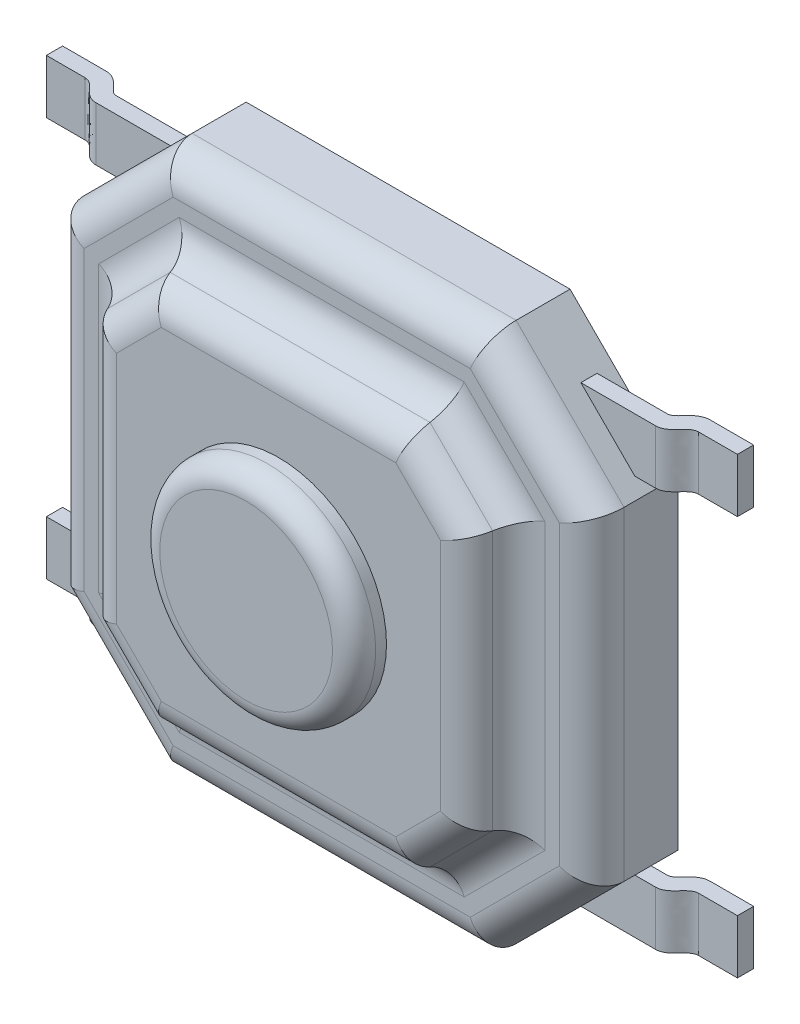
SolidWorks part; units mm, degrees
ref_plane "Front Plane" through (0, 0, 0) normal (0, 0, 1) x (1, 0, 0)
ref_plane "Top Plane" through (0, 0, 0) normal (0, 1, 0) x (1, 0, 0)
ref_plane "Right Plane" through (0, 0, 0) normal (1, 0, 0) x (0, 0, -1)
sketch "Sketch1" plane through (0, 0, 0) normal (0, 0, 1) x (1, 0, 0)
  line L0 (0, 0) -> (0, 2.5) construction
  line L1 (0, 0) -> (2.5, 0) construction
  line L2 (-1.5, 2.5) -> (1.5, 2.5)
  line L3 (1.5, 2.5) -> (2.5, 1.5)
  line L4 (2.5, 1.5) -> (2.5, -1.5)
  line L5 (1.5, -2.5) -> (2.5, -1.5)
  line L6 (-1.5, -2.5) -> (1.5, -2.5)
  line L7 (-1.5, -2.5) -> (-2.5, -1.5)
  line L8 (-2.5, 1.5) -> (-2.5, -1.5)
  line L9 (-1.5, 2.5) -> (-2.5, 1.5)
  point P13 (0, -2.5)
  dimension "D1" = 45
  dimension "D2" = 2.5
  dimension "D3" = 1.5
extrude "Boss-Extrude1" add sketch "Sketch1" along normal blind 0.8
sketch "Sketch2" plane through (0, 0, 0.8) normal (0, 0, 1) x (1, 0, 0)
  line L46 (-1.2101, 1.8) -> (-1.8, 1.2101)
  line L47 (-1.8, 1.2101) -> (-1.8, -1.2101)
  line L48 (-1.8, -1.2101) -> (-1.2101, -1.8)
  line L49 (-1.2101, -1.8) -> (1.2101, -1.8)
  line L50 (1.2101, -1.8) -> (1.8, -1.2101)
  line L51 (1.8, -1.2101) -> (1.8, 1.2101)
  line L52 (1.8, 1.2101) -> (1.2101, 1.8)
  line L53 (1.2101, 1.8) -> (-1.2101, 1.8)
  line L54 (-1.2101, 1.8) -> (-1.8, 1.2101)
  line L55 (-1.8, 1.2101) -> (-1.8, -1.2101)
  line L56 (-1.8, -1.2101) -> (-1.2101, -1.8)
  line L57 (-1.2101, -1.8) -> (1.2101, -1.8)
  line L58 (1.2101, -1.8) -> (1.8, -1.2101)
  line L59 (1.8, -1.2101) -> (1.8, 1.2101)
  line L60 (1.8, 1.2101) -> (1.2101, 1.8)
  line L61 (1.2101, 1.8) -> (-1.2101, 1.8)
  dimension "D1" = 0.7
extrude "Boss-Extrude2" add sketch "Sketch2" along normal offset from surface (0.4 mm away) 1.2 up to face at (0, 0, 0)
sketch "Sketch3" plane through (0, 0, 1.2) normal (0, 0, 1) x (1, 0, 0)
  circle A0 centre (0, 0) radius 1
  dimension "D1" = 2
extrude "Boss-Extrude3" add sketch "Sketch3" along normal offset from surface (0.3 mm away) 1.5 up to face at (0, 0, 0)
fillet "Fillet1" radius 0.3 8 edges at (-1.505, 1.505, 1.2) (0, 1.8, 1.2) (1.505, 1.505, 1.2) (1.8, 0, 1.2) (1.505, -1.505, 1.2) (0, -1.8, 1.2) (-1.505, -1.505, 1.2) (-1.8, 0, 1.2)
fillet "Fillet2" radius 0.3 8 edges at (-2, -2, 0.8) (0, -2.5, 0.8) (2, -2, 0.8) (2.5, 0, 0.8) (2, 2, 0.8) (0, 2.5, 0.8) (-2, 2, 0.8) (-2.5, 0, 0.8)
ref_plane "Plane1" through (0, 1.85, 0) normal (0, 1, 0) x (1, 0, 0)
fillet "Fillet3" radius 0.3 8 edges at (0, -1.8, 0.8) (1.505, -1.505, 0.8) (1.8, 0, 0.8) (1.505, 1.505, 0.8) (0, 1.8, 0.8) (-1.505, 1.505, 0.8) (-1.8, 0, 0.8) (-1.505, -1.505, 0.8)
fillet "Fillet4" radius 0.2 1 edges at (1, 0, 1.5)
sketch "Sketch4" plane through (0, 1.85, 0) normal (0, 1, 0) x (1, 0, 0)
  line L0 (0, -0.15) -> (-2.55, -0.15)
  line L1 (-3.2, 0) -> (-2.8, 0)
  line L2 (1.5, 0) -> (-1.5, 0) construction
  line L3 (0, 0) -> (0, -0.15) construction
  line L5 (-2.5, -0.5) -> (-2.5, 0) construction
  line L6 (-3.2, -0.15) -> (-2.8415, -0.15)
  line L7 (0, -0.3) -> (-2.5915, -0.3)
  line L8 (-3.2, 0) -> (-3.2, -0.15)
  line L9 (-2.8, 0) -> (-2.55, -0.15) construction
  line L10 (-2.8415, -0.15) -> (-2.5915, -0.3) construction
  line L11 (0, -0.15) -> (2.55, -0.15)
  line L12 (3.2, 0) -> (2.8, 0)
  line L13 (3.2, 0) -> (3.2, -0.15)
  line L14 (3.2, -0.15) -> (2.8415, -0.15)
  line L15 (0, -0.3) -> (2.5915, -0.3)
  spline S0 degree 3 poles (-2.8, 0) (-2.6624, 0) (-2.6305, -0.15) (-2.55, -0.15) knots 0 0 0 0 1 1 1 1
  spline S1 degree 3 poles (-2.5915, -0.3) (-2.7133, -0.3) (-2.7444, -0.15) (-2.8415, -0.15) knots 0 0 0 0 1 1 1 1
  spline S2 degree 3 poles (2.8, 0) (2.6624, 0) (2.6305, -0.15) (2.55, -0.15) knots 0 0 0 0 1 1 1 1
  spline S3 degree 3 poles (2.5915, -0.3) (2.7133, -0.3) (2.7444, -0.15) (2.8415, -0.15) knots 0 0 0 0 1 1 1 1
  dimension "D1" = 3.2
  dimension "D2" = 0.4
  dimension "D3" = 0.15
  dimension "D4" = 0.05
  dimension "D5" = 0.15
extrude "Boss-Extrude4" add sketch "Sketch4" along normal mid plane 0.5
mirror "Mirror1" about plane through (0, 0, 0) normal (0, 1, 0) of "Boss-Extrude4"
ref_axis "Axis1" through (0, 0, -0.075) along (0, 0, 1)
